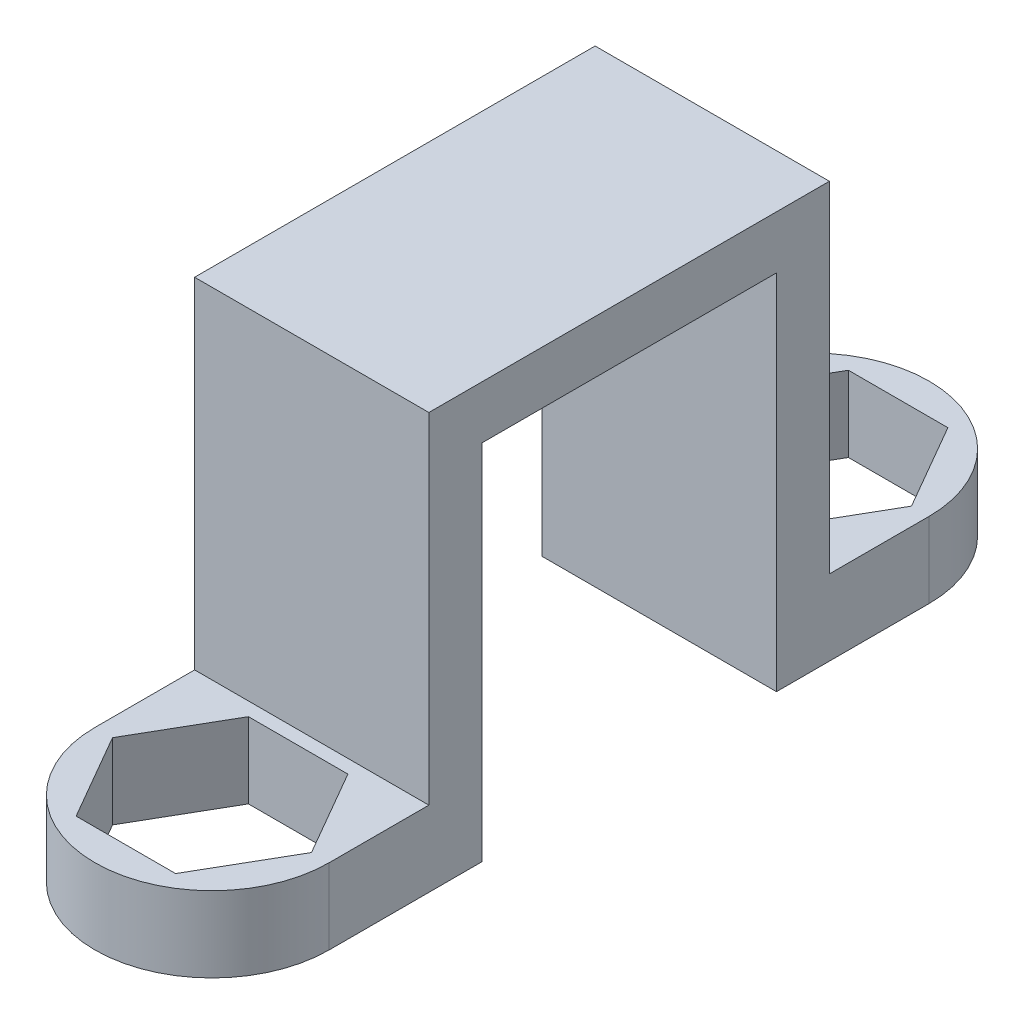
SolidWorks part; units mm, degrees
ref_plane "Přední rovina" through (0, 0, 0) normal (0, 0, 1) x (1, 0, 0)
ref_plane "Horní rovina" through (0, 0, 0) normal (0, 1, 0) x (1, 0, 0)
ref_plane "Pravá rovina" through (0, 0, 0) normal (1, 0, 0) x (0, 0, -1)
sketch "Sketch1" plane through (0, 0, 0) normal (1, 0, 0) x (0, 0, -1)
  line L0 (-4.875, 5.125) -> (-4.875, -6.875)
  line L1 (-6.625, 6.875) -> (6.625, 6.875)
  line L2 (-6.625, 6.875) -> (-6.625, -6.875)
  line L3 (-6.625, -6.875) -> (6.625, -6.875)
  line L4 (6.625, 6.875) -> (6.625, -6.875)
  line L5 (-6.625, 6.875) -> (6.625, -6.875) construction
  line L6 (-6.625, -6.875) -> (6.625, 6.875) construction
  line L7 (-4.875, 5.125) -> (4.875, 5.125)
  line L8 (4.875, 5.125) -> (4.875, -6.875)
  point P0 (0, 0)
  dimension "D1" = 1.75
  dimension "D2" = 1.75
  dimension "D3" = 1.75
  dimension "D4" = 9.75
  dimension "D5" = 12
extrude "Boss-Extrude1" add sketch "Sketch1" along normal blind 7.75 contours L7 L8 L3 L4 L1 L2 L0 region at (0, -0.875, 5.066)
sketch "Sketch2" plane through (0, -6.875, 0) normal (0, -1, 0) x (1, 0, 0)
  line L0 (3.875, 4.875) -> (3.875, 9.925) construction
  line L1 (0, 6.625) -> (0, 4.875) construction
  line L2 (0, 4.875) -> (0, 9.925)
  line L3 (7.75, 4.875) -> (7.75, 9.925)
  line L4 (7.75, 4.875) -> (0, 4.875) construction
  line L5 (7.75, 6.625) -> (7.75, 4.875) construction
  line L6 (7.75, 6.625) -> (0, 6.625) construction
  line L7 (7.75, 4.875) -> (0, 4.875)
  line L8 (2.2296, 12.775) -> (0.5841, 9.925)
  line L9 (0.5841, 9.925) -> (2.2296, 7.075)
  line L10 (2.2296, 7.075) -> (5.5204, 7.075)
  line L11 (5.5204, 7.075) -> (7.1659, 9.925)
  line L12 (7.1659, 9.925) -> (5.5204, 12.775)
  line L13 (5.5204, 12.775) -> (2.2296, 12.775)
  line L14 (0, 6.625) -> (0, -6.625) construction
  arc A0 (0, 4.875) -> (7.75, 4.875) centre (3.875, 4.875) ccw
  arc A1 (7.75, 9.925) -> (0, 9.925) centre (3.875, 9.925) ccw
  circle A3 centre (3.875, 9.925) radius 2.85 construction
  point P4 (3.875, 7.4)
  point P28 (0, 0)
  line M9 (7.75, 6.625) -> (0, 6.625)
  dimension "D1" = 5.7
  dimension "D3" = 9.925
  dimension "D2" = 3.3
extrude "Boss-Extrude2" add sketch "Sketch2" against normal blind 2.5 contours L3 A1 L2 M9 region at (0.1056, -6.875, 8.275)
mirror "Mirror1" about plane through (0, 0, 0) normal (0, 0, 1) of "Boss-Extrude2"
